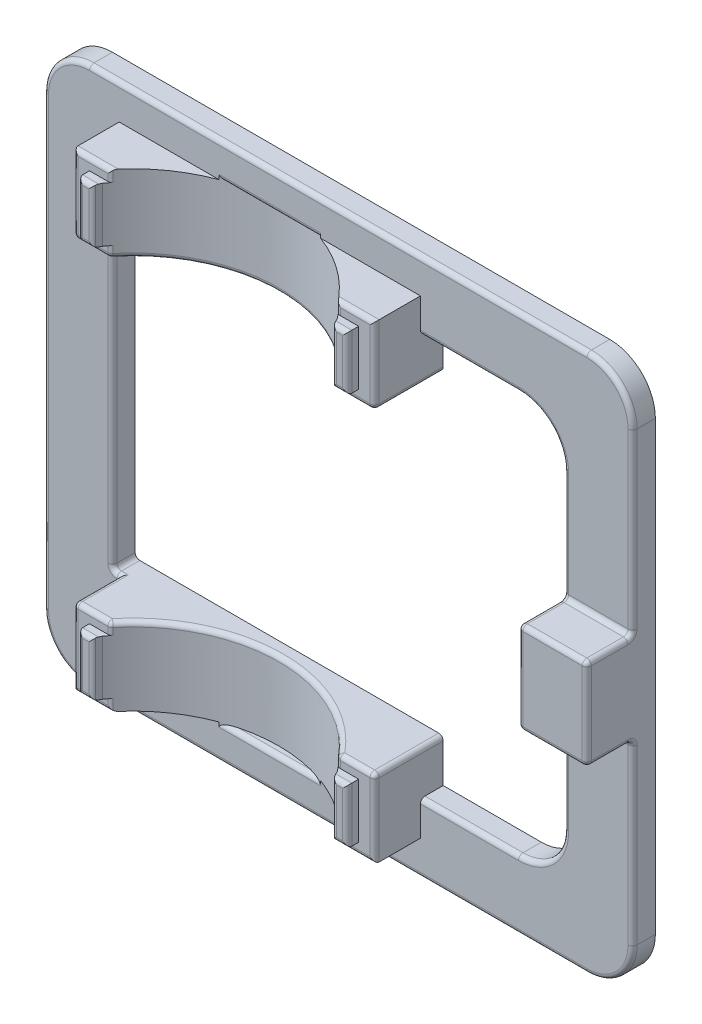
SolidWorks part; units mm, degrees
note: The reader was unsure of these and kept them because the rebuilt part matched: shared geometry of "Sketch6<2>".
ref_plane "Front Plane" through (0, 0, 0) normal (0, 0, 1) x (1, 0, 0)
ref_plane "Top Plane" through (0, 0, 0) normal (0, 1, 0) x (1, 0, 0)
ref_plane "Right Plane" through (0, 0, 0) normal (1, 0, 0) x (0, 0, -1)
sketch "Sketch1" plane through (0, 0, 0) normal (0, 0, 1) x (1, 0, 0)
  line L0 (-152.1159, -36.9329) -> (-92.1159, -36.9329)
  line L1 (-152.1159, -23.9668) -> (-92.1159, -23.9668)
  line L2 (-92.1159, 61.9993) -> (-152.1159, 61.9993)
  line L3 (-152.1159, 49.0332) -> (-92.1159, 49.0332)
  line L4 (-152.1159, 61.9993) -> (-152.1159, 49.0332)
  line L5 (-92.1159, 61.9993) -> (-92.1159, 49.0332)
  line L6 (-92.1159, -23.9668) -> (-92.1159, -36.9329)
  line L7 (-152.1159, -36.9329) -> (-152.1159, -23.9668)
  circle A0 centre (-139.6159, 44.7932) radius 1.6
  circle A1 centre (-139.6159, -19.7268) radius 1.6
  dimension "D1" = 3.2
  dimension "D2" = 92.1159
  dimension "D3" = 139.6159
  dimension "D4" = 152.1159
  dimension "D5" = 44.7932
  dimension "D6" = 49.0332
  dimension "D7" = 61.9993
  dimension "D8" = 19.7268
  dimension "D9" = 23.9668
sketch "Sketch2" plane through (0, 0, 0) normal (0, 0, 1) x (1, 0, 0)
  line L0 (-139.6159, 44.7932) -> (-139.6159, -19.7268) construction
  line L1 (-139.6159, 12.5332) -> (-108.8057, 12.5332) construction
  line L2 (-92.1159, 61.9993) -> (-92.1159, 49.0332) construction
  line L3 (-171.6159, 71.4993) -> (-42.6159, 71.4993)
  line L4 (-171.6159, 71.4993) -> (-171.6159, 12.5332)
  line L5 (-171.6159, 12.5332) -> (-42.6159, 12.5332)
  line L6 (-42.6159, 71.4993) -> (-42.6159, 12.5332)
  line L7 (-92.1159, 61.9993) -> (-152.1159, 61.9993) construction
  line L8 (-152.1159, 49.0332) -> (-92.1159, 49.0332) construction
  line L9 (-92.1159, 61.9993) -> (-92.1159, 49.0332)
  line L10 (-92.1159, 61.9993) -> (-152.1159, 61.9993)
  line L11 (-152.1159, 61.9993) -> (-152.1159, 49.0332)
  line L12 (-152.1159, 49.0332) -> (-92.1159, 49.0332)
  line L20 (-147.1159, 61.4993) -> (-147.1159, 49.5332)
  line L21 (-152.1159, 61.9993) -> (-152.1159, 49.0332) construction
  line L24 (-92.6159, 61.4993) -> (-151.6159, 61.4993)
  line L25 (-151.6159, 61.4993) -> (-151.6159, 49.5332)
  line L26 (-151.6159, 49.5332) -> (-92.6159, 49.5332)
  line L27 (-92.6159, 49.5332) -> (-92.6159, 61.4993)
  line L28 (-92.6159, 61.4993) -> (-151.6159, 61.4993)
  line L29 (-151.6159, 61.4993) -> (-151.6159, 49.5332)
  line L30 (-151.6159, 49.5332) -> (-92.6159, 49.5332)
  line L31 (-92.6159, 49.5332) -> (-92.6159, 61.4993)
  dimension "D2" = 5
  dimension "D3" = 20
  dimension "D4" = 50
  dimension "D5" = 10
  dimension "D1" = 0.5
extrude "Boss-Extrude1" add sketch "Sketch2" along normal blind 5 contours L6 L3 L4 L5 L31 L30 L29 L28
sketch "Sketch3" plane through (0, 0, 0) normal (0, 0, -1) x (-1, 0, 0)
  line L0 (152.1159, 49.0332) -> (156.6159, 49.0332)
  line L1 (57.6159, 56.4993) -> (156.6159, 56.4993)
  line L2 (57.6159, 56.4993) -> (57.6159, -4.4927)
  line L3 (57.6159, -4.4927) -> (156.6159, -4.4927)
  line L4 (42.6159, 12.5332) -> (171.6159, 12.5332)
  line L5 (171.6159, 12.5332) -> (171.6159, 71.4993)
  line L6 (171.6159, 71.4993) -> (42.6159, 71.4993)
  line L7 (42.6159, 71.4993) -> (42.6159, 12.5332)
  line L8 (42.6159, 12.5332) -> (171.6159, 12.5332)
  line L9 (171.6159, 12.5332) -> (171.6159, 71.4993)
  line L10 (171.6159, 71.4993) -> (42.6159, 71.4993)
  line L11 (42.6159, 71.4993) -> (42.6159, 12.5332)
  line L12 (156.6159, 56.4993) -> (156.6159, -4.4927)
  line M8 (42.6159, 12.5332) -> (171.6159, 12.5332)
  line M14 (152.1159, 49.0332) -> (92.1159, 49.0332)
  line M15 (92.1159, 49.0332) -> (92.1159, 61.9993)
  dimension "D2" = 15
  dimension "D3" = 15
  dimension "D4" = 15
  dimension "D1" = 0
extrude "Cut-Extrude1" cut sketch "Sketch3" against normal blind 5 contours L12 L0 L1 L2 M14 M15 M8
sketch "Sketch4" plane through (0, 71.4993, 0) normal (0, 1, 0) x (1, 0, 0)
  line L0 (-171.6159, -5) -> (-42.6159, -5) construction
  line L1 (-171.6159, 0) -> (-42.6159, 0) construction
  line L2 (-89.1159, 0) -> (-155.1159, 0)
  line L3 (-89.1159, 0) -> (-89.1159, -15.025)
  line L4 (-89.1159, -15.025) -> (-155.1159, -15.025)
  line L5 (-155.1159, 0) -> (-155.1159, -15.025)
  line L6 (-92.1159, 0) -> (-152.1159, 0) construction
  line L7 (-92.1159, 0) -> (-152.1159, 0)
  line L8 (-122.1159, 0) -> (-122.1159, -35)
  line L9 (-147.1159, 0) -> (-147.1159, -62.5244)
  circle A0 centre (-122.1159, -35) radius 30
  circle A1 centre (-122.1159, -35) radius 32
  point P16 (-147.1159, 0)
  point P22 (-147.1159, -15.025)
  dimension "D1" = 60
  dimension "D3" = 2
  dimension "D2" = 30
  dimension "D4" = 3
  dimension "D5" = 3
extrude "Boss-Extrude2" add sketch "Sketch4" against normal up to vertex from surface
sketch "Sketch5" plane through (0, 0, 15.025) normal (0, 0, 1) x (1, 0, 0)
  line L0 (-92.1159, 61.9993) -> (-152.1159, 61.9993) construction
  line L1 (-92.1159, 61.9993) -> (-152.1159, 61.9993)
  line L2 (-122.1159, 61.9993) -> (-122.1159, 57.1229)
  line L3 (-151.6159, 49.5332) -> (-92.6159, 49.5332) construction
  line L4 (-147.1159, 61.9993) -> (-155.1159, 61.9993)
  line L5 (-155.1159, 61.9993) -> (-155.1159, 49.0332)
  line L6 (-155.1159, 49.0332) -> (-147.1159, 49.0332)
  line L7 (-147.1159, 49.0332) -> (-147.1159, 61.9993)
  line L8 (-147.1159, 61.9993) -> (-155.1159, 61.9993)
  line L9 (-155.1159, 61.9993) -> (-155.1159, 49.0332)
  line L10 (-155.1159, 49.0332) -> (-147.1159, 49.0332)
  line L11 (-147.1159, 49.0332) -> (-147.1159, 61.9993)
  line L12 (-92.6159, 61.4993) -> (-151.6159, 61.4993) construction
  line L13 (-147.1159, 61.4993) -> (-147.1159, 49.5332) construction
  line L14 (-151.6159, 61.4993) -> (-151.6159, 49.5332) construction
  line L15 (-151.6159, 49.5332) -> (-92.6159, 49.5332)
  line L16 (-92.6159, 61.4993) -> (-151.6159, 61.4993)
  line L17 (-147.1159, 61.4993) -> (-147.1159, 49.5332)
  line L18 (-151.6159, 61.4993) -> (-151.6159, 49.5332)
  line L19 (-97.1159, 49.0332) -> (-97.1159, 61.9993)
  line L20 (-92.6159, 61.4993) -> (-92.6159, 49.5332)
  dimension "D1" = 0
extrude "Boss-Extrude3" add sketch "Sketch5" along normal blind 2.5 contours L16 L18 L15 L11 | L20 L16 L19 L15
chamfer "Chamfer1" distance 3 distance2 1.5 1 edges at (-147.1159, 55.5163, 17.525)
chamfer "Chamfer2" distance 1.5 distance2 3 1 edges at (-97.1159, 55.5163, 17.525)
sketch "Sketch6" plane through (0, 49.0332, 0) normal (0, -1, 0) x (1, 0, 0)
  line L7 (-155.1159, 15.025) -> (-155.1159, 5)
  line L8 (-155.1159, 5) -> (-156.6159, 5)
  line L9 (-156.6159, 5) -> (-156.6159, 0)
  line L10 (-156.6159, 0) -> (-89.1159, 0)
  line L11 (-89.1159, 0) -> (-89.1159, 15.025)
  line L12 (-89.1159, 15.025) -> (-97.1159, 15.025)
  line L13 (-147.1159, 15.025) -> (-155.1159, 15.025)
  line L14 (-155.1159, 15.025) -> (-155.1159, 5)
  line L15 (-155.1159, 5) -> (-156.6159, 5)
  line L16 (-156.6159, 5) -> (-156.6159, 0)
  line L17 (-156.6159, 0) -> (-89.1159, 0)
  line L18 (-89.1159, 0) -> (-89.1159, 15.025)
  line L19 (-89.1159, 15.025) -> (-97.1159, 15.025)
  line L20 (-147.1159, 15.025) -> (-155.1159, 15.025)
  arc A1 (-147.1159, 15.025) -> (-97.1159, 15.025) centre (-122.1159, 35) ccw
  arc A2 (-147.1159, 15.025) -> (-97.1159, 15.025) centre (-122.1159, 35) ccw
  dimension "D1" = 0
extrude "Boss-Extrude4" add sketch "Sketch6" along normal blind 2
extrude "Boss-Extrude5" add sketch "Sketch6<2>" against normal blind 2 from surface at -12.9661 starting at face at (-122.1159, 61.9993, 4)
sketch "Sketch6<2>" plane through (0, 49.0332, 0) normal (0, -1, 0) x (1, 0, 0) same geometry as "Sketch6"
sketch "Sketch7" plane through (0, 61.9993, 0) normal (0, -1, 0) x (1, 0, 0)
  line L1 (-110.9804, 5) -> (-133.2514, 5)
  line L2 (-110.9804, 5) -> (-133.2514, 5)
  arc A1 (-133.2514, 5) -> (-110.9804, 5) centre (-122.1159, 35) ccw
  arc A2 (-133.2514, 5) -> (-110.9804, 5) centre (-122.1159, 35) ccw
  dimension "D1" = 0
extrude "Cut-Extrude2" cut sketch "Sketch7" against normal up to surface (2 mm away) up to face at (-96.4114, 63.9993, 9.7766)
sketch "Sketch9" plane through (0, 0, 5) normal (0, 0, 1) x (1, 0, 0)
  line L0 (-42.6159, 71.4993) -> (-42.6159, 12.5332) construction
  line L1 (-57.6159, 12.5332) -> (-42.6159, 12.5332)
  line L2 (-57.6159, 12.5332) -> (-57.6159, 22.5332)
  line L3 (-57.6159, 22.5332) -> (-42.6159, 22.5332)
  line L4 (-42.6159, 12.5332) -> (-42.6159, 22.5332)
  dimension "D1" = 10
extrude "Boss-Extrude6" add sketch "Sketch9" along normal up to surface (10.025 mm away) up to face at (-93.9909, 55.5163, 15.025)
fillet "Fillet2" radius 10 3 edges at (-57.6159, 56.4993, 2.5) (-42.6159, 71.4993, 2.5) (-171.6159, 71.4993, 2.5)
fillet "Fillet3" radius 1 1 edges at (-156.6159, 47.0332, 2.5)
fillet "Fillet4" radius 1 39 edges at (-57.6159, 34.5163, 5) (-60.5448, 53.5704, 5) (-155.3659, 47.0332, 5) (-156.323, 46.7403, 5) (-171.6159, 37.0163, 5) (-168.6869, 68.5704, 5) (-107.1159, 71.4993, 5) (-45.5448, 68.5704, 5) (-92.6159, 55.5163, 17.525) (-94.1159, 49.5332, 17.525) (-95.6159, 55.5163, 17.525) (-94.1159, 61.4993, 17.525) (-151.6159, 55.5163, 17.525) (-150.1159, 61.4993, 17.525) (-148.6159, 55.5163, 17.525) (-150.1159, 49.5332, 17.525) (-78.3659, 56.4993, 5) (-156.6159, 29.2832, 5) (-42.6159, 42.0163, 5) (-147.1159, 48.2832, 15.025) (-97.1159, 48.2832, 15.025) (-151.1159, 63.9993, 15.025) (-147.1159, 62.7493, 15.025) (-97.1159, 62.7493, 15.025) (-93.1159, 63.9993, 15.025) (-89.1159, 55.5163, 15.025) (-93.1159, 47.0332, 15.025) (-151.1159, 47.0332, 15.025) (-155.1159, 55.5163, 15.025) (-155.1159, 47.0332, 10.0125) (-122.1159, 63.9993, 5) (-122.1159, 47.0332, 3) (-89.1159, 47.0332, 7.5125) (-57.6159, 22.5332, 10.0125) (-50.1159, 22.5332, 5) (-42.6159, 22.5332, 10.0125) (-50.1159, 22.5332, 15.025) (-42.6159, 17.5332, 15.025) (-57.6159, 17.5332, 15.025)
mirror "Mirror3" about plane through (-171.6159, 12.5332, 5) normal (0, 1, 0) of bodies 110 108
